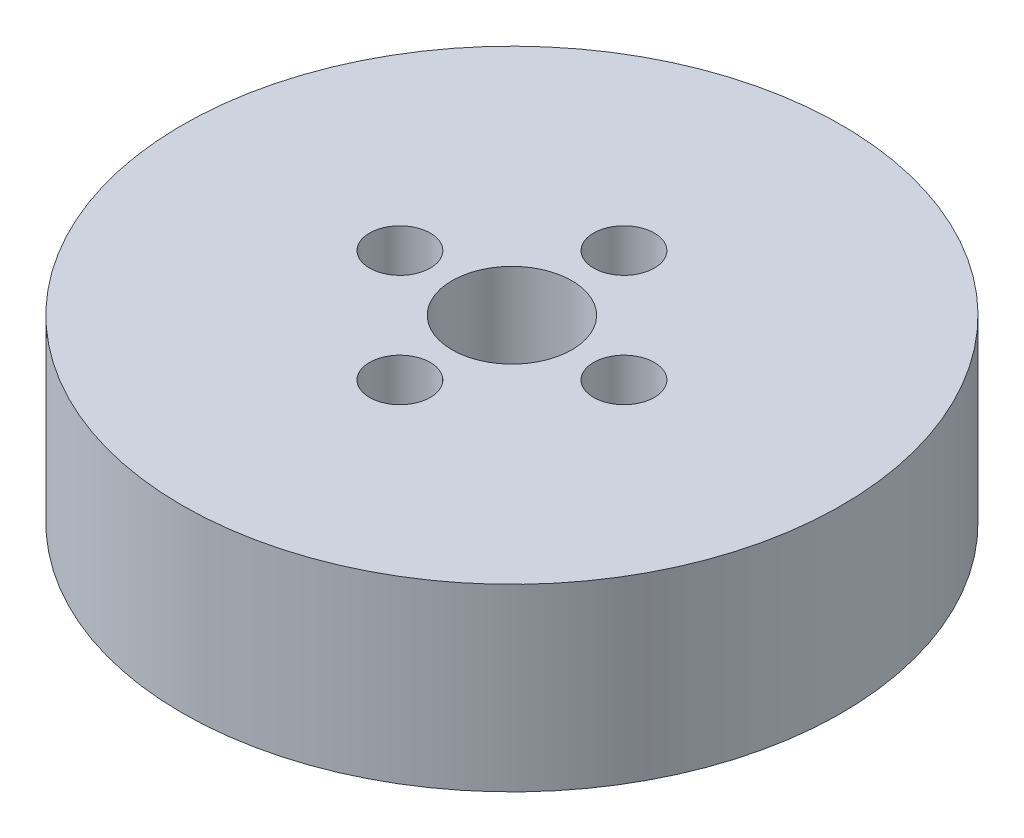
SolidWorks part; units mm, degrees
ref_plane "Front Plane" through (0, 0, 0) normal (0, 0, 1) x (1, 0, 0)
ref_plane "Top Plane" through (0, 0, 0) normal (0, 1, 0) x (1, 0, 0)
ref_plane "Right Plane" through (0, 0, 0) normal (1, 0, 0) x (0, 0, -1)
sketch "Sketch1" plane through (0, 0, 0) normal (0, 1, 0) x (1, 0, 0)
  circle A0 centre (0, 0) radius 27.5
  dimension "FLANGE_OD" = 55
extrude "Boss-Extrude1" add sketch "Sketch1" along normal blind 15
sketch "Sketch2" plane through (0, 0, 0) normal (0, 1, 0) x (1, 0, 0)
  circle A0 centre (0, 0) radius 5
  dimension "BORE_D" = 10
extrude "Cut-Extrude1" cut sketch "Sketch2" along normal through all
sketch "Sketch3" plane through (0, 15, 0) normal (0, 1, 0) x (1, 0, 0)
  circle A0 centre (0, 0) radius 9.3478 construction
  circle A1 centre (-9.3478, 0) radius 2.5347
  dimension "BOLT_D" = 5.0693
  dimension "BOLT_PCD" = 18.6957
extrude "Cut-Extrude2" cut sketch "Sketch3" against normal blind 11.6839
pattern_circular "CirPattern1" count 4 over 360 about axis through (0, 0, 0) along (0, 1, 0) of "Cut-Extrude2"
